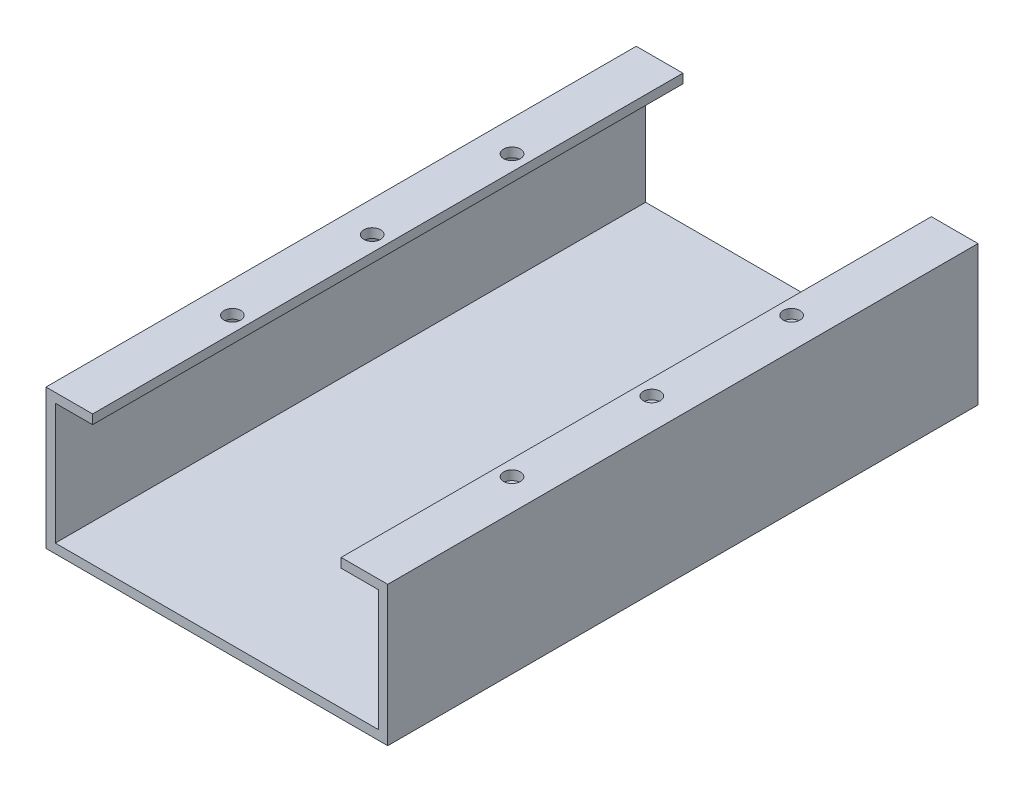
SolidWorks part; units mm, degrees
ref_plane "前视基准面" through (0, 0, 0) normal (0, 0, 1) x (1, 0, 0)
ref_plane "上视基准面" through (0, 0, 0) normal (0, 1, 0) x (1, 0, 0)
ref_plane "右视基准面" through (0, 0, 0) normal (1, 0, 0) x (0, 0, -1)
sketch "草图1" plane through (0, 0, 0) normal (0, 0, 1) x (1, 0, 0)
  line L0 (0, -10) -> (110, -10)
  line L1 (110, -10) -> (110, 35)
  line L2 (110, 35) -> (95, 35)
  line L3 (95, 35) -> (95, 32)
  line L4 (0, -10) -> (0, 35)
  line L5 (0, 35) -> (15, 35)
  line L6 (15, 35) -> (15, 32)
  line L7 (15, 32) -> (3, 32)
  line L8 (3, 32) -> (3, -7)
  line L9 (3, -7) -> (107, -7)
  line L10 (107, -7) -> (107, 32)
  line L11 (107, 32) -> (95, 32)
  point P13 (0, 0)
  point P14 (0, 0)
  point P15 (0, 0)
  point P16 (0, 0)
extrude "凸台-拉伸1" add sketch "草图1" along normal blind 110
sketch "草图2" plane through (0, 35, 0) normal (0, 1, 0) x (1, 0, 0)
  circle A0 centre (10, -10) radius 2.7
  circle A1 centre (100, -10) radius 2.7
  circle A2 centre (100, -55) radius 2.7
  circle A3 centre (100, -100) radius 2.7
  circle A4 centre (10, -55) radius 2.7
  circle A5 centre (10, -100) radius 2.7
  dimension "D1" = 2
  dimension "D2" = 3
extrude "切除-拉伸1" cut sketch "草图2" against normal blind 3
sketch "草图3" plane through (0, 0, 110) normal (0, 0, 1) x (1, 0, 0)
  line L0 (15, 32) -> (15, 35)
  line L1 (15, 35) -> (0, 35)
  line L2 (0, 35) -> (0, -10)
  line L3 (0, -10) -> (110, -10)
  line L4 (110, -10) -> (110, 35)
  line L5 (110, 35) -> (95, 35)
  line L6 (95, 35) -> (95, 32)
  line L7 (95, 32) -> (107, 32)
  line L8 (107, 32) -> (107, -7)
  line L9 (107, -7) -> (3, -7)
  line L10 (3, -7) -> (3, 32)
  line L11 (3, 32) -> (15, 32)
extrude "凸台-拉伸2" add sketch "草图3" along normal blind 40
pattern_linear "阵列(线性)1" count 2 spacing 150 along (0, 0, -1) of "凸台-拉伸2"
